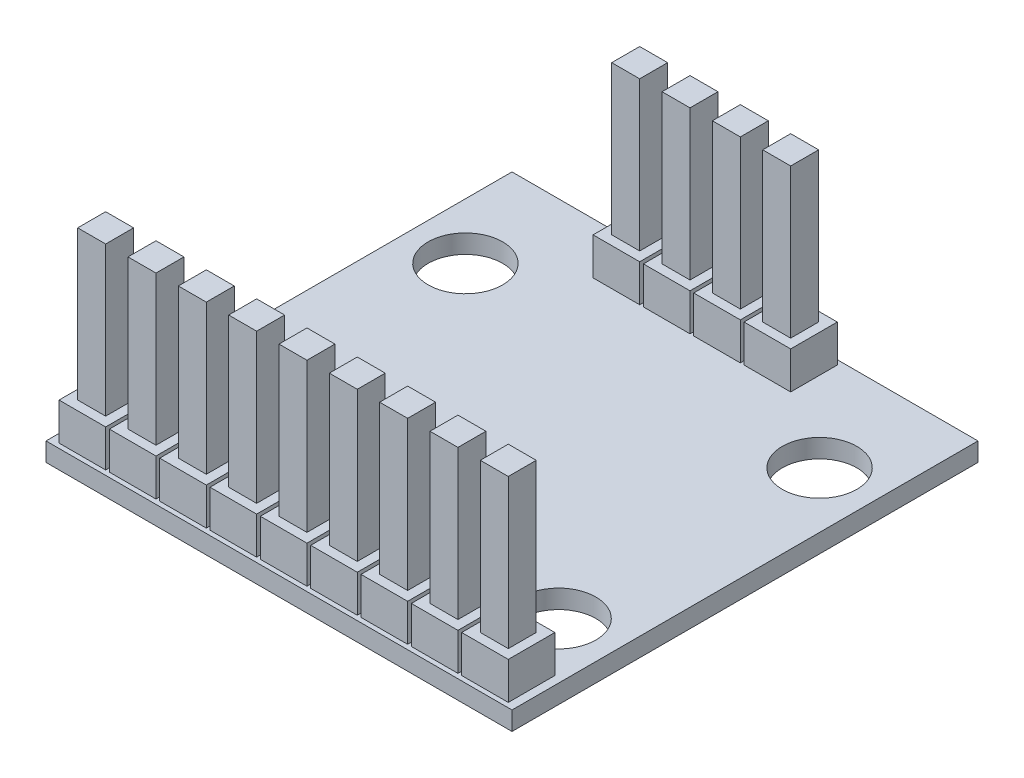
SolidWorks part; units mm, degrees
ref_plane "Спереди" through (0, 0, 0) normal (0, 0, 1) x (1, 0, 0)
ref_plane "Сверху" through (0, 0, 0) normal (0, 1, 0) x (1, 0, 0)
ref_plane "Справа" through (0, 0, 0) normal (1, 0, 0) x (0, 0, -1)
sketch "Эскиз1" plane through (0, 0, 0) normal (0, 1, 0) x (1, 0, 0)
  line L0 (1.45, -9.75) -> (3.95, -9.75)
  line L1 (12.5, -12.5) -> (-12.5, -12.5)
  line L2 (12.5, -12.5) -> (12.5, 12.5)
  line L3 (12.5, 12.5) -> (-12.5, 12.5)
  line L4 (-12.5, -12.5) -> (-12.5, 12.5)
  line L5 (12.5, -12.5) -> (-12.5, 12.5) construction
  line L6 (12.5, 12.5) -> (-12.5, -12.5) construction
  line L7 (9.5, -7) -> (-9.5, -7) construction
  line L8 (9.5, -7) -> (9.5, 7) construction
  line L9 (9.5, 7) -> (-9.5, 7) construction
  line L10 (-9.5, -7) -> (-9.5, 7) construction
  line L11 (9.5, -7) -> (-9.5, 7) construction
  line L12 (9.5, 7) -> (-9.5, -7) construction
  line L13 (-12.5, -11) -> (12.5, -11) construction
  line L15 (-1.25, -9.75) -> (1.25, -9.75)
  line L16 (-1.25, -9.75) -> (-1.25, -12.25)
  line L17 (-1.25, -12.25) -> (1.25, -12.25)
  line L18 (1.25, -9.75) -> (1.25, -12.25)
  line L19 (-1.25, -9.75) -> (1.25, -12.25) construction
  line L20 (-1.25, -12.25) -> (1.25, -9.75) construction
  line L36 (-1.25, -12.25) -> (1.35, -12.25) construction
  line L37 (-3.95, -12.25) -> (-1.45, -12.25)
  line L38 (-3.95, -9.75) -> (-1.45, -9.75)
  line L39 (-1.45, -9.75) -> (-1.45, -12.25)
  line L40 (-3.95, -9.75) -> (-3.95, -12.25)
  line L41 (-6.65, -12.25) -> (-4.15, -12.25)
  line L42 (-6.65, -9.75) -> (-4.15, -9.75)
  line L43 (-4.15, -9.75) -> (-4.15, -12.25)
  line L44 (-6.65, -9.75) -> (-6.65, -12.25)
  line L45 (-9.35, -12.25) -> (-6.85, -12.25)
  line L46 (-9.35, -9.75) -> (-6.85, -9.75)
  line L47 (-6.85, -9.75) -> (-6.85, -12.25)
  line L48 (-9.35, -9.75) -> (-9.35, -12.25)
  line L49 (-12.05, -12.25) -> (-9.55, -12.25)
  line L50 (-12.05, -9.75) -> (-9.55, -9.75)
  line L51 (-9.55, -9.75) -> (-9.55, -12.25)
  line L52 (-12.05, -9.75) -> (-12.05, -12.25)
  line L53 (-1.25, -12.25) -> (-3.95, -12.25) construction
  line L54 (1.45, -9.75) -> (1.45, -12.25)
  line L55 (-12.5, 11) -> (12.5, 11) construction
  line L56 (0, 12.25) -> (2.5, 12.25)
  line L57 (-2.7, 12.25) -> (-0.2, 12.25)
  line L58 (-2.7, 12.25) -> (-2.7, 9.75)
  line L59 (-2.7, 9.75) -> (-0.2, 9.75)
  line L60 (-0.2, 12.25) -> (-0.2, 9.75)
  line L61 (-2.7, 12.25) -> (-0.2, 9.75) construction
  line L62 (-2.7, 9.75) -> (-0.2, 12.25) construction
  line L63 (0, 12.25) -> (0, 9.75)
  line L64 (2.5, 12.25) -> (2.5, 9.75)
  line L65 (0, 9.75) -> (2.5, 9.75)
  line L66 (2.7, 12.25) -> (5.2, 12.25)
  line L67 (2.7, 12.25) -> (2.7, 9.75)
  line L68 (5.2, 12.25) -> (5.2, 9.75)
  line L69 (2.7, 9.75) -> (5.2, 9.75)
  line L70 (-2.7, 12.25) -> (0, 12.25) construction
  line L71 (-5.4, 9.75) -> (-2.9, 9.75)
  line L72 (-2.9, 12.25) -> (-2.9, 9.75)
  line L73 (-5.4, 12.25) -> (-2.9, 12.25)
  line L74 (-5.4, 12.25) -> (-5.4, 9.75)
  line L75 (-2.7, 9.75) -> (-5.4, 9.75) construction
  line L76 (1.45, -12.25) -> (3.95, -12.25)
  line L77 (3.95, -9.75) -> (3.95, -12.25)
  line L78 (1.45, -9.75) -> (3.95, -12.25) construction
  line L79 (1.45, -12.25) -> (3.95, -9.75) construction
  line L80 (1.45, -12.25) -> (4.05, -12.25) construction
  line L81 (4.15, -9.75) -> (6.65, -9.75)
  line L82 (4.15, -9.75) -> (4.15, -12.25)
  line L83 (4.15, -12.25) -> (6.65, -12.25)
  line L84 (6.65, -9.75) -> (6.65, -12.25)
  line L85 (4.15, -9.75) -> (6.65, -12.25) construction
  line L86 (4.15, -12.25) -> (6.65, -9.75) construction
  line L87 (4.15, -12.25) -> (6.75, -12.25) construction
  line L88 (6.85, -9.75) -> (9.35, -9.75)
  line L89 (6.85, -9.75) -> (6.85, -12.25)
  line L90 (6.85, -12.25) -> (9.35, -12.25)
  line L91 (9.35, -9.75) -> (9.35, -12.25)
  line L92 (6.85, -9.75) -> (9.35, -12.25) construction
  line L93 (6.85, -12.25) -> (9.35, -9.75) construction
  line L94 (6.85, -12.25) -> (9.45, -12.25) construction
  line L95 (9.55, -9.75) -> (12.05, -9.75)
  line L96 (9.55, -9.75) -> (9.55, -12.25)
  line L97 (9.55, -12.25) -> (12.05, -12.25)
  line L98 (12.05, -9.75) -> (12.05, -12.25)
  line L99 (9.55, -9.75) -> (12.05, -12.25) construction
  line L100 (9.55, -12.25) -> (12.05, -9.75) construction
  line L101 (9.55, -12.25) -> (12.15, -12.25) construction
  line L102 (0, -11) -> (2.7, -11) construction
  circle A0 centre (-9.5, 7) radius 2
  circle A1 centre (9.5, 7) radius 2
  circle A2 centre (9.5, -7) radius 2
  circle A3 centre (-9.5, -7) radius 2
  point P0 (0, 0)
  point P6 (0, 0)
  point P17 (0, -11)
  point P26 (2.7, -11)
  point P33 (5.4, -11)
  point P60 (-1.45, 11)
  point P66 (0, 11)
  point P67 (8.1, -11)
  point P89 (10.8, -11)
  dimension "D5" = 4
  dimension "D1" = 25
  dimension "D2" = 25
  dimension "D3" = 19
  dimension "D4" = 14
  dimension "D6" = 1.5
  dimension "D7" = 2.5
  dimension "D8" = 2.5
  dimension "D10" = 2.6
  dimension "D12" = 2.7
  dimension "D13" = 1.5
  dimension "D14" = 1.45
  dimension "D16" = 2.7
  dimension "D18" = 2.7
  dimension "D19" = 2.7
  dimension "D11" = 5
  dimension "D15" = 3
  dimension "D17" = 2
  dimension "D9" = 5
extrude "Бобышка-Вытянуть1" add sketch "Эскиз1" along normal blind 1
extrude "Бобышка-Вытянуть3" add sketch "Эскиз1<4>" along normal blind 3 contours L50 L52 L49 L51 | L46 L48 L45 L47 | L38 L40 L37 L39 | L18 L15 L16 L17 | L67 L69 L68 L66 | L63 L65 L64 L56 | L60 L57 L58 L59 | L73 L74 L71 L72 | L77 L0 L54 L76 | L84 L81 L82 L83 | L91 L88 L89 L90 | L98 L95 L96 L97 | L42 L43 L41 L44 region at (2.7, 0, 11) region at (0, 0, 11) region at (-2.7, 0, 11) region at (-8.1, 0, 11) region at (-10.8, 0, 11) region at (1.25, 0, -11) region at (-1.45, 0, -11) region at (3.95, 0, -11) region at (-4.15, 0, -11) region at (5.4, 0, 11) region at (8.1, 0, 11) region at (10.8, 0, 11)
sketch "Эскиз1<4>" plane through (0, 0, 0) normal (0, 1, 0) x (1, 0, 0) same geometry as "Эскиз1"
sketch "Эскиз3" plane through (0, 3, 0) normal (0, 1, 0) x (1, 0, 0)
  line L12 (-3.4, 11.75) -> (-4.9, 11.75)
  line L13 (-4.9, 11.75) -> (-4.9, 10.25)
  line L14 (-4.9, 10.25) -> (-3.4, 10.25)
  line L15 (-3.4, 10.25) -> (-3.4, 11.75)
  line L16 (-3.4, 11.75) -> (-4.9, 11.75)
  line L17 (-4.9, 11.75) -> (-4.9, 10.25)
  line L18 (-4.9, 10.25) -> (-3.4, 10.25)
  line L19 (-3.4, 10.25) -> (-3.4, 11.75)
  line L20 (-0.7, 11.75) -> (-2.2, 11.75)
  line L21 (-2.2, 11.75) -> (-2.2, 10.25)
  line L22 (-2.2, 10.25) -> (-0.7, 10.25)
  line L23 (-0.7, 10.25) -> (-0.7, 11.75)
  line L32 (2, 11.75) -> (0.5, 11.75)
  line L33 (0.5, 11.75) -> (0.5, 10.25)
  line L34 (0.5, 10.25) -> (2, 10.25)
  line L35 (2, 10.25) -> (2, 11.75)
  line L44 (4.7, 11.75) -> (3.2, 11.75)
  line L45 (3.2, 11.75) -> (3.2, 10.25)
  line L46 (3.2, 10.25) -> (4.7, 10.25)
  line L47 (4.7, 10.25) -> (4.7, 11.75)
  line L52 (-3.4, 11.75) -> (-0.7, 11.75) construction
  line L53 (-7.35, -10.25) -> (-8.85, -10.25)
  line L54 (-8.85, -10.25) -> (-8.85, -11.75)
  line L55 (-8.85, -11.75) -> (-7.35, -11.75)
  line L56 (-10.05, -10.25) -> (-11.55, -10.25)
  line L57 (-11.55, -10.25) -> (-11.55, -11.75)
  line L58 (-11.55, -11.75) -> (-10.05, -11.75)
  line L59 (-10.05, -11.75) -> (-10.05, -10.25)
  line L60 (-10.05, -10.25) -> (-11.55, -10.25)
  line L61 (-11.55, -10.25) -> (-11.55, -11.75)
  line L62 (-11.55, -11.75) -> (-10.05, -11.75)
  line L63 (-10.05, -11.75) -> (-10.05, -10.25)
  line L64 (-7.35, -11.75) -> (-7.35, -10.25)
  line L65 (-4.65, -10.25) -> (-6.15, -10.25)
  line L66 (-6.15, -10.25) -> (-6.15, -11.75)
  line L67 (-6.15, -11.75) -> (-4.65, -11.75)
  line L68 (-4.65, -11.75) -> (-4.65, -10.25)
  line L69 (-1.95, -10.25) -> (-3.45, -10.25)
  line L70 (-3.45, -10.25) -> (-3.45, -11.75)
  line L71 (-3.45, -11.75) -> (-1.95, -11.75)
  line L72 (-1.95, -11.75) -> (-1.95, -10.25)
  line L73 (0.75, -10.25) -> (-0.75, -10.25)
  line L74 (-0.75, -10.25) -> (-0.75, -11.75)
  line L75 (-0.75, -11.75) -> (0.75, -11.75)
  line L76 (0.75, -11.75) -> (0.75, -10.25)
  line L77 (3.45, -10.25) -> (1.95, -10.25)
  line L78 (1.95, -10.25) -> (1.95, -11.75)
  line L79 (1.95, -11.75) -> (3.45, -11.75)
  line L80 (3.45, -11.75) -> (3.45, -10.25)
  line L81 (6.15, -10.25) -> (4.65, -10.25)
  line L82 (4.65, -10.25) -> (4.65, -11.75)
  line L83 (4.65, -11.75) -> (6.15, -11.75)
  line L84 (6.15, -11.75) -> (6.15, -10.25)
  line L85 (8.85, -10.25) -> (7.35, -10.25)
  line L86 (7.35, -10.25) -> (7.35, -11.75)
  line L87 (7.35, -11.75) -> (8.85, -11.75)
  line L88 (8.85, -11.75) -> (8.85, -10.25)
  line L89 (11.55, -10.25) -> (10.05, -10.25)
  line L90 (10.05, -10.25) -> (10.05, -11.75)
  line L91 (10.05, -11.75) -> (11.55, -11.75)
  line L92 (11.55, -11.75) -> (11.55, -10.25)
  line L93 (-10.05, -10.25) -> (-7.35, -10.25) construction
  dimension "D3" = 2.7
  dimension "D6" = 2.7
  dimension "D1" = 0.5
  dimension "D2" = 4
  dimension "D4" = 9
  dimension "D5" = 0.5
extrude "Бобышка-Вытянуть4" add sketch "Эскиз3" along normal blind 8
scale "Масштаб1" scale about origin uniform scaling yes scale factor 0.04
